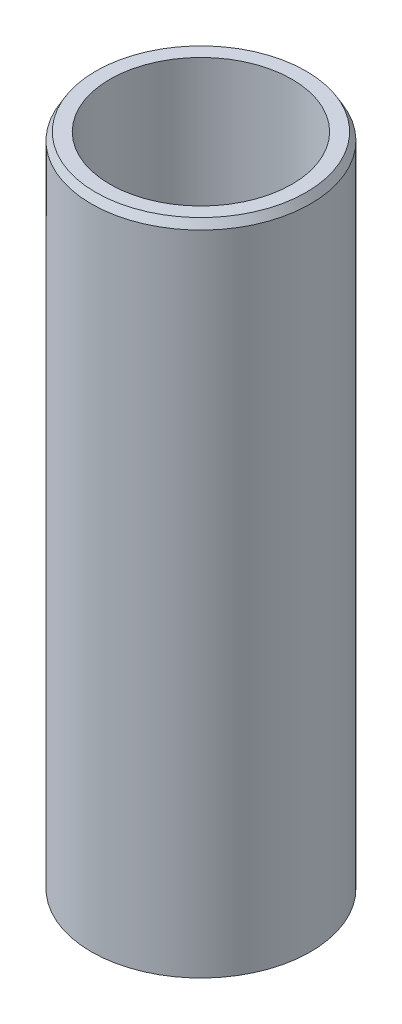
SolidWorks part; units mm, degrees
ref_plane "Front Plane" through (0, 0, 0) normal (0, 0, 1) x (1, 0, 0)
ref_plane "Top Plane" through (0, 0, 0) normal (0, 1, 0) x (1, 0, 0)
ref_plane "Right Plane" through (0, 0, 0) normal (1, 0, 0) x (0, 0, -1)
sketch "Sketch1" plane through (0, 0, 0) normal (0, 1, 0) x (1, 0, 0)
  circle A0 centre (0, 0) radius 57.5
  dimension "SHAFT_OD" = 115
extrude "Boss-Extrude1" add sketch "Sketch1" along normal blind 346.2028
sketch "Sketch2" plane through (0, 0, 0) normal (0, 1, 0) x (1, 0, 0)
  circle A0 centre (0, 0) radius 47.7497
  dimension "BORE_D" = 95.4994
extrude "Cut-Extrude1" cut sketch "Sketch2" along normal through all
chamfer "Chamfer1" distance 4.0497 angle 30 2 edges at (0, 346.2028, 57.5) (0, 0, 57.5) first distance on face at (0, 346.2028, 57.5) first distance on face at (0, 0, 47.7497)
